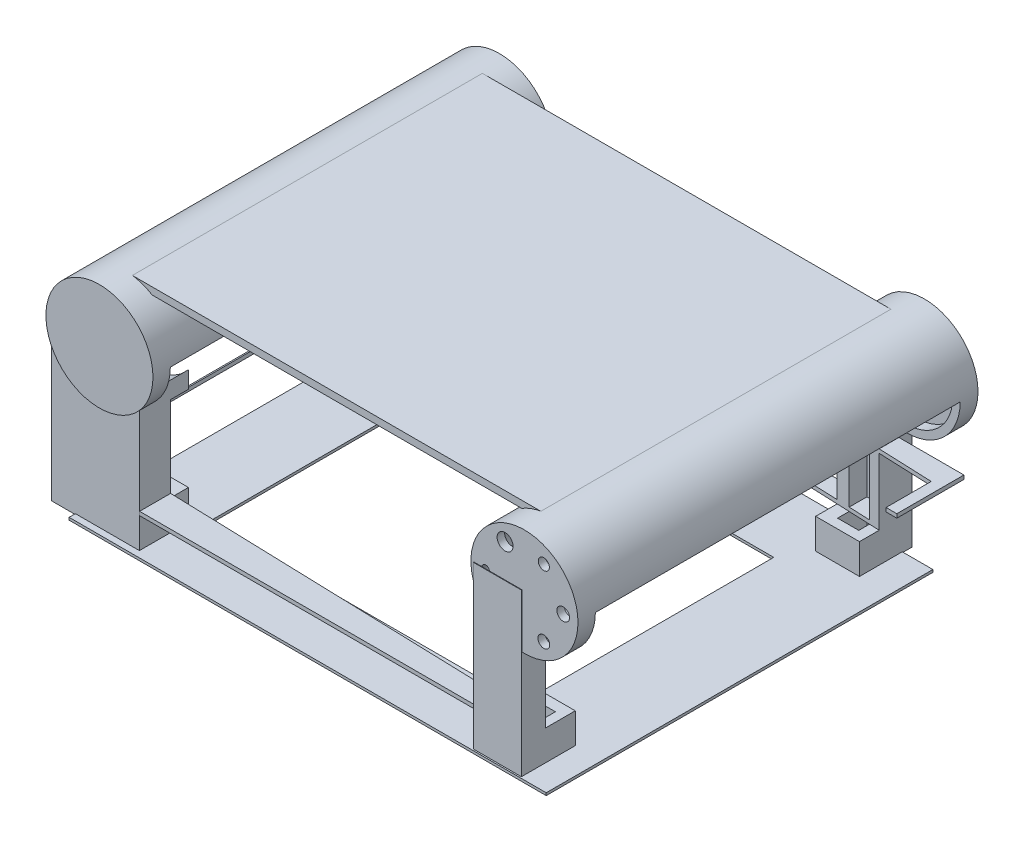
SolidWorks part; units mm, degrees
ref_plane "Front Plane" through (0, 0, 0) normal (0, 0, 1) x (1, 0, 0)
ref_plane "Top Plane" through (0, 0, 0) normal (0, 1, 0) x (1, 0, 0)
ref_plane "Right Plane" through (0, 0, 0) normal (1, 0, 0) x (0, 0, -1)
sketch "MotorHoldersSketch" plane through (0, 0, 0) normal (0, 0, 1) x (1, 0, 0)
  line L0 (0, 0) -> (170, 0) construction
  line L1 (0, 0) -> (0, 21.41) construction
  line L2 (170, 0) -> (170, 21.41) construction
  circle A0 centre (0, 0) radius 21.41
  circle A1 centre (170, 0) radius 21.41
ref_axis "MotorCenterAxis1" through (0, 0, 0) along (0, 0, 1)
ref_axis "MotorCenterAxis2" through (170, 0, 0) along (0, 0, 1)
extrude "MotorHolders" add sketch "MotorHoldersSketch" along normal blind 80 and the other way blind 80
sketch "Sketch3" plane through (0, 0, 0) normal (0, 0, 1) x (1, 0, 0)
  line L1 (1.9406, 21.133) -> (168.3435, 21.133)
  line L2 (1.9406, 21.133) -> (1.9406, 18.3155)
  line L3 (1.9406, 18.3155) -> (168.3435, 18.3155)
  line L4 (168.3435, 21.133) -> (168.3435, 18.3155)
extrude "Boss-Extrude2" add sketch "Sketch3" along normal blind 70 and the other way blind 70
sketch "Sketch4" plane through (0, 0, 0) normal (0, 1, 0) x (1, 0, 0)
  line L1 (221.2811, -73.0508) -> (-41.4939, -73.0508)
  line L2 (221.2811, -73.0508) -> (221.2811, 72.8691)
  line L3 (221.2811, 72.8691) -> (-41.4939, 72.8691)
  line L4 (-41.4939, -73.0508) -> (-41.4939, 72.8691)
extrude "Cut-Extrude1" cut sketch "Sketch4" against normal blind 23
ref_axis "Axis3" through (170, 0, 0) along (0, -1, 0)
sketch3d "ReferencePlanePosition"
  line L0 (170, 0, 0) -> (170, -34.8293, 0)
  line L1 (170, 0, 0) -> (170, -38.994, 0) construction
ref_plane "ReferencePlane" through (170, -34.8293, 0) normal (0, -1, 0) x (-1, 0, 0)
sketch "Sketch6" plane through (170, -34.8293, 0) normal (0, -1, 0) x (-1, 0, 0)
  line L1 (191.0664, 78.949) -> (154.5717, 78.949)
  line L2 (191.0664, 78.949) -> (191.0664, 56.3099)
  line L3 (191.0664, 56.3099) -> (154.5717, 56.3099)
  line L4 (154.5717, 78.949) -> (154.5717, 56.3099)
  line L5 (190.894, -58.6712) -> (155.7267, -58.6712)
  line L6 (190.894, -58.6712) -> (190.894, -78.2822)
  line L7 (190.894, -78.2822) -> (155.7267, -78.2822)
  line L8 (155.7267, -58.6712) -> (155.7267, -78.2822)
  line L9 (20.2985, 77.8627) -> (2.7559, 77.8627)
  line L10 (20.2985, 77.8627) -> (20.2985, 56.7633)
  line L11 (20.2985, 56.7633) -> (2.7559, 56.7633)
  line L12 (2.7559, 77.8627) -> (2.7559, 56.7633)
  line L13 (20.1677, -58.6712) -> (1.0007, -58.6712)
  line L14 (20.1677, -58.6712) -> (20.1677, -80.2189)
  line L15 (20.1677, -80.2189) -> (1.0007, -80.2189)
  line L16 (1.0007, -58.6712) -> (1.0007, -80.2189)
  line L17 (188.8265, 72.2461) -> (157.7696, 72.2461)
  line L18 (188.8265, 72.2461) -> (188.8265, 60.5121)
  line L19 (188.8265, 60.5121) -> (157.7696, 60.5121)
  line L20 (157.7696, 72.2461) -> (157.7696, 60.5121)
  line L21 (15.2746, 72.2461) -> (6.7922, 72.2461)
  line L22 (15.2746, 72.2461) -> (15.2746, 60.5121)
  line L23 (15.2746, 60.5121) -> (6.7922, 60.5121)
  line L24 (6.7922, 72.2461) -> (6.7922, 60.5121)
  line L25 (15.2746, -72.8101) -> (4.6276, -72.8101)
  line L26 (15.2746, -72.8101) -> (15.2746, -62.9794)
  line L27 (15.2746, -62.9794) -> (4.6276, -62.9794)
  line L28 (4.6276, -72.8101) -> (4.6276, -62.9794)
  line L29 (188.0744, -72.8101) -> (160.3766, -72.8101)
  line L30 (188.0744, -72.8101) -> (188.0744, -62.9794)
  line L31 (188.0744, -62.9794) -> (160.3766, -62.9794)
  line L32 (160.3766, -72.8101) -> (160.3766, -62.9794)
extrude "PowerBankHolders" add sketch "Sketch6" along normal blind 30 and the other way blind 35 separate body
sketch3d "3DSketch3"
  line L0 (170, 0, 0) -> (170, -64.5, 0) construction
ref_plane "Plane2" through (170, -64.5, 0) normal (0, -1, 0) x (-1, 0, 0)
sketch "Sketch7" plane through (170, -64.5, 0) normal (0, -1, 0) x (-1, 0, 0)
  line L1 (-9.5047, -80.801) -> (181.32, -80.801)
  line L2 (-9.5047, -80.801) -> (-9.5047, 73.8662)
  line L3 (-9.5047, 73.8662) -> (181.32, 73.8662)
  line L4 (181.32, -80.801) -> (181.32, 73.8662)
  line L5 (151.8712, -54.3972) -> (26.5361, -54.3972)
  line L6 (151.8712, -54.3972) -> (151.8712, 46.2413)
  line L7 (151.8712, 46.2413) -> (26.5361, 46.2413)
  line L8 (26.5361, -54.3972) -> (26.5361, 46.2413)
extrude "TopCellPhoneCover" add sketch "Sketch7" along normal blind 1
ref_point "Point1"
ref_point "Point2"
sketch3d "3DSketch11"
  line L0 (0, 0, -80) -> (170, 0, 80) construction
  point P4 (85, 0, 0)
sketch "MotorHolderExtrudeSketch" plane through (0, 0, 0) normal (0, 0, 1) x (1, 0, 0)
  circle A0 centre (170, 0) radius 18.415
  circle A1 centre (0, 0) radius 18.415
  circle A3 centre (0, 0) radius 21.41 construction
  circle A4 centre (170, 0) radius 21.41 construction
extrude "MotorHolderExtrude" cut sketch "MotorHolderExtrudeSketch" against normal blind 77 and the other way blind 77
ref_point "TopOfMotors"
ref_plane "TangentToTopOfMotors" through (0, -18.415, 0) normal (0, 1, 0) x (1, 0, 0)
ref_axis "Axis4" through (85, 0, 0) along (0, -1, 0)
ref_plane "BottomOfPowerBankRegion" through (0, -18.425, 0) normal (0, 1, 0) x (1, 0, 0)
sketch "Sketch11" plane through (0, -18.425, 0) normal (0, 1, 0) x (1, 0, 0)
  line L0 (-18.9327, 3.7419) -> (188.9327, -3.7419) construction
  line L5 (-18.9327, -64.7581) -> (-18.9327, 72.2419)
  line L6 (188.9327, 63.7581) -> (188.9327, -71.2419)
  line L7 (188.9327, -71.2419) -> (-18.9327, -64.7581)
  line L8 (188.9327, 63.7581) -> (-18.9327, 72.2419)
  circle A0 centre (85, 0) radius 104 construction
extrude "Cut-Extrude9" cut sketch "Sketch11" against normal blind 10
ref_point "CenterAtBottomOfPowerBank"
ref_plane "TopOfPowerBankPlane" through (0, -52.425, 0) normal (0, 1, 0) x (1, 0, 0)
sketch "Sketch13" plane through (0, -52.425, 0) normal (0, 1, 0) x (1, 0, 0)
  line L1 (-19.4498, 72.5454) -> (166.1636, 72.5454)
  line L2 (-19.4498, 72.5454) -> (-19.4498, -78.2051)
  line L3 (-19.4498, -78.2051) -> (166.1636, -78.2051)
  line L4 (166.1636, 72.5454) -> (166.1636, -78.2051)
  line L5 (19.3173, -49.583) -> (137.9607, -49.583)
  line L6 (19.3173, -49.583) -> (19.3173, -21.0549)
  line L7 (19.3173, -21.0549) -> (137.9607, -21.0549)
  line L8 (137.9607, -49.583) -> (137.9607, -21.0549)
  line L9 (19.3173, 56.6778) -> (137.9607, 56.6778)
  line L10 (19.3173, 56.6778) -> (19.3173, 36.3234)
  line L11 (19.3173, 36.3234) -> (137.9607, 36.3234)
  line L12 (137.9607, 56.6778) -> (137.9607, 36.3234)
  line L13 (19.3173, 18.3186) -> (137.9607, 18.3186)
  line L14 (19.3173, 18.3186) -> (19.3173, -7.3615)
  line L15 (19.3173, -7.3615) -> (137.9607, -7.3615)
  line L16 (137.9607, 18.3186) -> (137.9607, -7.3615)
extrude "TopOfPowerBankExtrude" add sketch "Sketch13" along normal blind 1.5
sketch "Sketch15" plane through (167.2441, 0, 0) normal (1, 0, 0) x (0, 0, -1)
  line L1 (72.5313, -25.7765) -> (45.7099, -25.7765)
  line L2 (72.5313, -25.7765) -> (72.5313, -24.2242)
  line L3 (72.5313, -24.2242) -> (45.7099, -24.2242)
  line L4 (45.7099, -25.7765) -> (45.7099, -24.2242)
extrude "PowerBankSmallHolder1" add sketch "Sketch15" along normal blind 26
extrude "PowerBankExtrude" cut sketch "Sketch11<2>" against normal blind 34
sketch "Sketch11<2>" plane through (0, -18.425, 0) normal (0, 1, 0) x (1, 0, 0) same geometry as "Sketch11"
ref_plane "Plane6" through (0, 0, 0) normal (0, 0, 1) x (1, 0, 0)
sketch "Sketch16" plane through (0, 0, 0) normal (0, 0, 1) x (1, 0, 0)
  line L0 (170, 0) -> (170, -13.42)
  line L1 (170, 0) -> (170, -34.8293) construction
  line L2 (170, -13.42) -> (162.25, -13.42) construction
  line L3 (170, -13.42) -> (177.75, -13.42) construction
  line L5 (170, 0) -> (185.5, 0) construction
  line L6 (170, 0) -> (154.5, 0) construction
  line L7 (170, 0) -> (170, 13.42) construction
  line L8 (170, 0) -> (170, 21.41) construction
  line L9 (170, 13.42) -> (177.75, 13.42) construction
  line L10 (170, 13.42) -> (162.25, 13.42)
ref_axis "BoltAxisA" through (185.5, 0, 0) along (0, 0, 1)
ref_axis "BoltAxisB" through (177.75, -13.42, 0) along (0, 0, 1)
ref_axis "BoltAxisC" through (162.25, -13.42, 0) along (0, 0, 1)
ref_axis "BoltAxisD" through (154.5, 0, 0) along (0, 0, 1)
ref_axis "BoltAxisE" through (162.25, 13.42, 0) along (0, 0, 1)
ref_axis "BoltAxisF" through (177.75, 13.42, 0) along (0, 0, 1)
ref_point "Point6"
ref_point "Point7"
ref_point "Point8"
ref_point "Point9"
ref_point "Point10"
ref_point "Point11"
sketch "Sketch17" plane through (0, 0, 80) normal (0, 0, 1) x (1, 0, 0)
  circle A0 centre (185.5, 0) radius 2.532
  circle A1 centre (177.75, -13.42) radius 2.3608
  circle A2 centre (162.25, -13.42) radius 2.8435
  circle A3 centre (154.5, 0) radius 1.5122
  circle A4 centre (162.25, 13.42) radius 3.1928
  circle A5 centre (177.75, 13.42) radius 2.2218
extrude "Cut-Extrude11" cut sketch "Sketch17" against normal blind 31.5
